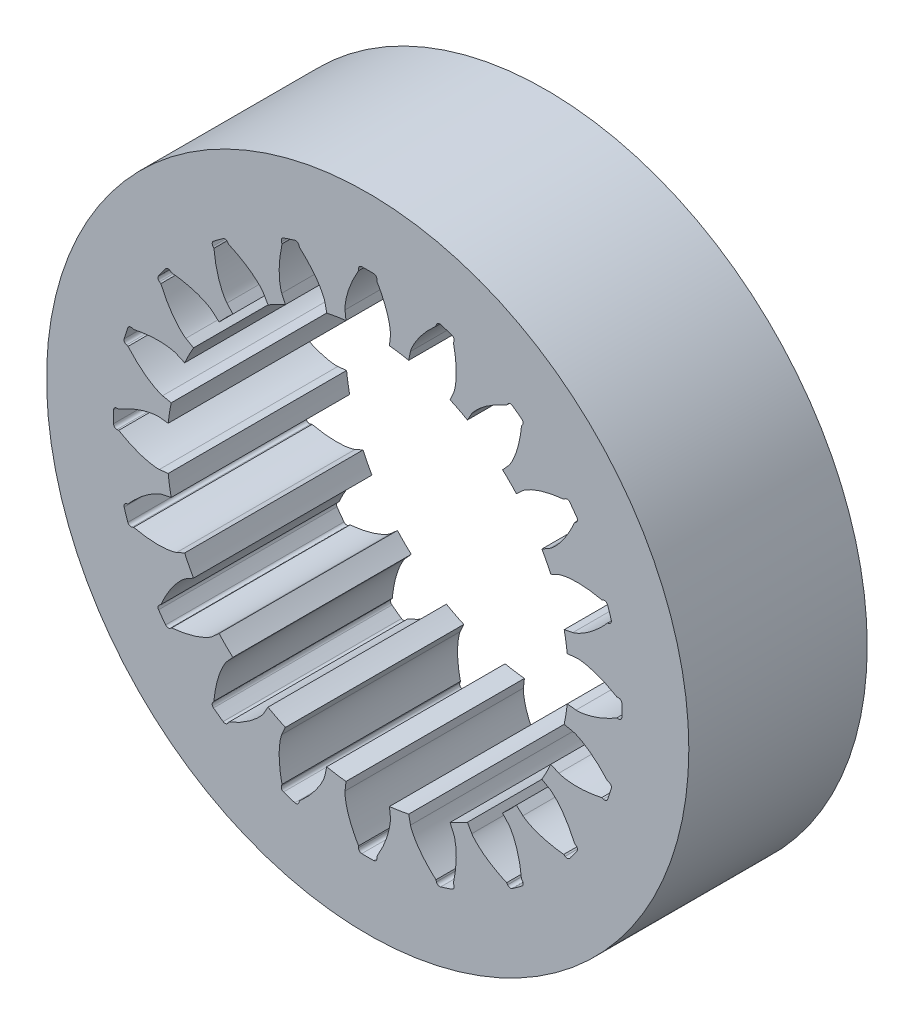
SolidWorks part; units mm, degrees
ref_plane "Front Plane" through (0, 0, 0) normal (0, 0, 1) x (1, 0, 0)
ref_plane "Top Plane" through (0, 0, 0) normal (0, 1, 0) x (1, 0, 0)
ref_plane "Right Plane" through (0, 0, 0) normal (1, 0, 0) x (0, 0, -1)
ref_axis "Gear Axis" through (0, 0, -0.5001) along (0, 0, 1)
sketch "Blank Sketch" plane through (0, 0, 0) normal (0, 0, 1) x (1, 0, 0)
  circle A0 centre (0, 0) radius 18
  circle A1 centre (0, 0) radius 11.25
  dimension "Rim" = 36
  dimension "Tip" = 22.5
extrude "Blank" add sketch "Blank Sketch" along normal blind 10
sketch "Tooth Space Sketch" plane through (0, 0, 0) normal (0, 0, 1) x (1, 0, 0)
  line L0 (11.6772, 1.2713) -> (9.9413, 1.0823)
  line L1 (11.6772, -1.2713) -> (9.9413, -1.0823)
  line L2 (9.9413, 1.0823) -> (9.9413, -1.0823)
  line L3 (13.9593, 0.5126) -> (14.0518, 0.516)
  line L4 (13.9593, -0.5126) -> (14.0518, -0.516)
  circle A0 centre (0, 0) radius 10 construction
  arc A1 (14.2461, 0.333) -> (14.0518, 0.516) centre (14.0587, 0.3286) ccw
  arc A2 (14.0518, -0.516) -> (14.2461, -0.333) centre (14.0587, -0.3286) ccw
  arc A3 (14.2461, -0.333) -> (14.2461, 0.333) centre (0, 0) ccw
  spline S0 degree 4 poles (11.6772, 1.2713) (11.6807, 1.2716) (11.6908, 1.2725) (11.7099, 1.2734) (11.741, 1.274) (11.7808, 1.2736) (11.8323, 1.2717) (11.8931, 1.2675) (11.9598, 1.261) (12.0324, 1.2518) (12.1048, 1.2409) (12.177, 1.2282) (12.2488, 1.214) (12.3357, 1.1951) (12.4397, 1.1698) (12.561, 1.1366) (12.6981, 1.0945) (12.8374, 1.0471) (12.9739, 0.9967) (13.1112, 0.9413) (13.2436, 0.8848) (13.3803, 0.8216) (13.5062, 0.7611) (13.6462, 0.6884) (13.759, 0.6283) (13.9066, 0.544) (13.9934, 0.4927) (14.0947, 0.4308) (14.1394, 0.4025) (14.1669, 0.385) knots 0 0 0 0 0 0.005377 0.015084 0.028532 0.04661 0.064855 0.092111 0.119476 0.146842 0.174209 0.201575 0.228941 0.256307 0.307035 0.361767 0.4165 0.471232 0.525964 0.580697 0.635429 0.690161 0.744894 0.799626 0.854358 0.909091 0.954545 1 1 1 1 1 construction
  spline S1 degree 4 poles (11.6772, 1.2713) (11.6807, 1.2716) (11.6908, 1.2725) (11.7099, 1.2734) (11.741, 1.274) (11.7808, 1.2736) (11.8323, 1.2717) (11.8931, 1.2675) (11.9598, 1.261) (12.0324, 1.2518) (12.1048, 1.2409) (12.177, 1.2282) (12.2488, 1.214) (12.3357, 1.1951) (12.4397, 1.1698) (12.561, 1.1366) (12.6981, 1.0945) (12.8374, 1.0471) (12.9739, 0.9967) (13.1112, 0.9413) (13.2436, 0.8848) (13.3803, 0.8216) (13.5062, 0.7611) (13.6462, 0.6884) (13.759, 0.6283) (13.8746, 0.5623) (13.9307, 0.5296) (13.9593, 0.5126) knots 0 0 0 0 0 0.005377 0.015084 0.028532 0.04661 0.064855 0.092111 0.119476 0.146842 0.174209 0.201575 0.228941 0.256307 0.307035 0.361767 0.4165 0.471232 0.525964 0.580697 0.635429 0.690161 0.744894 0.799626 0.854358 0.909091 0.909091 0.909091 0.909091 0.909091
  spline S2 degree 4 poles (11.6772, -1.2713) (11.6807, -1.2716) (11.6908, -1.2725) (11.7099, -1.2734) (11.741, -1.274) (11.7808, -1.2736) (11.8323, -1.2717) (11.8931, -1.2675) (11.9598, -1.261) (12.0324, -1.2518) (12.1048, -1.2409) (12.177, -1.2282) (12.2488, -1.214) (12.3357, -1.1951) (12.4397, -1.1698) (12.561, -1.1366) (12.6981, -1.0945) (12.8374, -1.0471) (12.9739, -0.9967) (13.1112, -0.9413) (13.2436, -0.8848) (13.3803, -0.8216) (13.5062, -0.7611) (13.6462, -0.6884) (13.759, -0.6283) (13.9066, -0.544) (13.9934, -0.4927) (14.0947, -0.4308) (14.1394, -0.4025) (14.1669, -0.385) knots 0 0 0 0 0 0.005377 0.015084 0.028532 0.04661 0.064855 0.092111 0.119476 0.146842 0.174209 0.201575 0.228941 0.256307 0.307035 0.361767 0.4165 0.471232 0.525964 0.580697 0.635429 0.690161 0.744894 0.799626 0.854358 0.909091 0.954545 1 1 1 1 1 construction
  spline S3 degree 4 poles (11.6772, -1.2713) (11.6807, -1.2716) (11.6908, -1.2725) (11.7099, -1.2734) (11.741, -1.274) (11.7808, -1.2736) (11.8323, -1.2717) (11.8931, -1.2675) (11.9598, -1.261) (12.0324, -1.2518) (12.1048, -1.2409) (12.177, -1.2282) (12.2488, -1.214) (12.3357, -1.1951) (12.4397, -1.1698) (12.561, -1.1366) (12.6981, -1.0945) (12.8374, -1.0471) (12.9739, -0.9967) (13.1112, -0.9413) (13.2436, -0.8848) (13.3803, -0.8216) (13.5062, -0.7611) (13.6462, -0.6884) (13.759, -0.6283) (13.8746, -0.5623) (13.9307, -0.5296) (13.9593, -0.5126) knots 0 0 0 0 0 0.005377 0.015084 0.028532 0.04661 0.064855 0.092111 0.119476 0.146842 0.174209 0.201575 0.228941 0.256307 0.307035 0.361767 0.4165 0.471232 0.525964 0.580697 0.635429 0.690161 0.744894 0.799626 0.854358 0.909091 0.909091 0.909091 0.909091 0.909091
  dimension "Root" = 14.25
  dimension "Fillet" = 0.1875
  dimension "Cap" = 20
extrude "Tooth Space" cut sketch "Tooth Space Sketch" against normal through all both and the other way through all both
pattern_circular "Teeth" count 20 over 360 about axis through (0, 0, -0.5001) along (0, 0, 1) of "Tooth Space"
equation "\"No. of Teeth\"= 20"
equation "\"Module\"= 1.25"
equation "\"Pressure Angle\"= 20"
equation "\"Inner Diameter\"= ( \"No. of Teeth\" - 2 ) * \"Module\""
equation "\"Pitch Diameter\"= \"No. of Teeth\" * \"Module\""
equation "\"Backlash\"= 0.3 * \"Module\""
equation "\"Arc Length\"= ( ( \"Module\" * pi ) / 2 + \"Backlash\" )"
equation "\"Fillet Radius\"= 0.15 * \"Module\""
equation "\"Tooth Depth\"= IIF ( \"Module\" <= 1.25 , \"Module\" * 2.4 , \"Module\" * 2.25 )"
equation "\"Face Width\"= 10"
equation "\"Root Diameter\"= \"Inner Diameter\" + 2 * \"Tooth Depth\""
equation "\"Rim Diameter\"= \"Root Diameter\" + 6 * \"Module\""
equation "\"Base Diameter\"= \"Pitch Diameter\" * cos ( \"Pressure Angle\" )"
equation "\"Base Radius\"= \"Base Diameter\" / 2"
equation "\"Tooth Thickness\"= \"Module\" * pi - \"Arc Length\""
equation "\"Half Space Angle\"= ( \"Arc Length\" / \"Pitch Diameter\" ) * 180 / pi"
equation "\"Involute Fn\"= tan ( \"Pressure Angle\" ) - \"Pressure Angle\" * pi / 180"
equation "\"Flank Offset\"= 0 - \"Arc Length\" / \"Pitch Diameter\" - \"Involute Fn\""
equation "\"Tip Cap Diameter\"= \"Inner Diameter\" - 2 * \"Module\""
equation "\"Flank Start Diameter\"= IIF ( \"Base Diameter\" >= ( \"Inner Diameter\" - \"Module\" ) , \"Base Diameter\" , \"Inner Diameter\" - \"Module\" )"
equation "\"Flank End Diameter\"= \"Root Diameter\" - 3 * \"Fillet Radius\""
equation "\"Involute t1\"= ( abs ( ( \"Flank Start Diameter\" / \"Base Diameter\" ) ^ 2 - 1 ) ) ^ 0.5"
equation "\"Involute t2\"= ( abs ( ( \"Flank End Diameter\" / \"Base Diameter\" ) ^ 2 - 1 ) ) ^ 0.5"
equation "\"Flank Arc Radius\"= ( \"Pitch Diameter\" / 2 ) * sin ( \"Pressure Angle\" )"
equation "\"Flank Centre Angle\"= \"Half Space Angle\" - \"Pressure Angle\""
equation "\"Rim@Blank Sketch\"= \"Rim Diameter\""
equation "\"Tip@Blank Sketch\"= \"Inner Diameter\""
equation "\"Width@Blank\"= \"Face Width\""
equation "\"Root@Tooth Space Sketch\"= \"Root Diameter\" / 2"
equation "\"Fillet@Tooth Space Sketch\"= \"Fillet Radius\""
equation "\"Cap@Tooth Space Sketch\"= \"Tip Cap Diameter\""
equation "\"Count@Teeth\"= \"No. of Teeth\""
